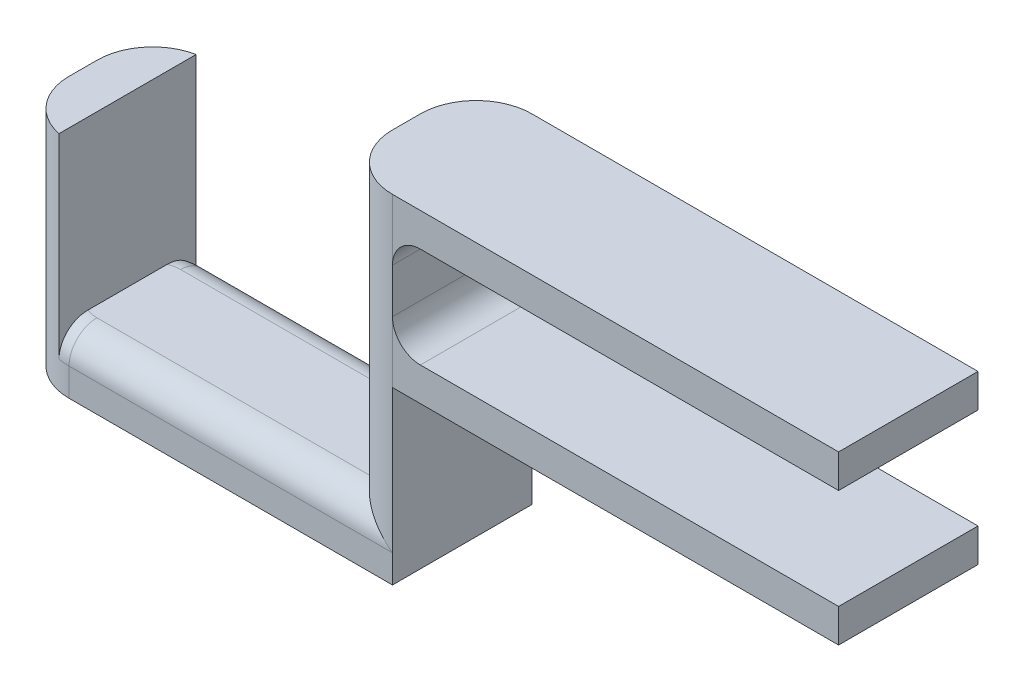
SolidWorks part; units mm, degrees
ref_plane "前基準面" through (0, 0, 0) normal (0, 0, 1) x (1, 0, 0)
ref_plane "上基準面" through (0, 0, 0) normal (0, 1, 0) x (1, 0, 0)
ref_plane "右基準面" through (0, 0, 0) normal (1, 0, 0) x (0, 0, -1)
sketch "草圖1" plane through (0, 0, 0) normal (0, 0, 1) x (1, 0, 0)
  line L2 (-55.2938, 11.9758) -> (-55.2938, -28.0242)
  line L4 (-47.2938, 11.9758) -> (-47.2938, -18.0242)
  line L5 (-47.2938, -18.0242) -> (2.7062, -18.0242)
  line L7 (-55.2938, -28.0242) -> (12.7062, -28.0242)
  line L10 (2.7062, -18.0242) -> (2.7062, 32.6478)
  line L12 (12.7062, -28.0242) -> (12.7062, 2.6478)
  line L13 (2.7062, 32.6478) -> (92.7062, 32.6478)
  line L15 (17.7062, 26.6478) -> (92.7062, 26.6478)
  line L16 (92.7062, 32.6478) -> (92.7062, 26.6478)
  line L17 (17.7062, 8.6478) -> (92.7062, 8.6478)
  line L19 (12.7062, 2.6478) -> (92.7062, 2.6478)
  line L20 (92.7062, 8.6478) -> (92.7062, 2.6478)
  line L21 (-55.2938, 11.9758) -> (-47.2938, 11.9758)
  line L24 (12.7062, 21.6478) -> (12.7062, 13.6478)
  arc A0 (17.7062, 26.6478) -> (12.7062, 21.6478) centre (17.7062, 21.6478) ccw
  arc A1 (17.7062, 8.6478) -> (12.7062, 13.6478) centre (17.7062, 13.6478) cw
  point P1 (92.7062, 29.6478)
  dimension "D12" = 80
  dimension "D1" = 50
  dimension "D2" = 10
  dimension "D3" = 10
  dimension "D4" = 8
  dimension "D5" = 6
  dimension "D6" = 6
  dimension "D7" = 30
  dimension "D8" = 40
  dimension "D9" = 10
  dimension "D10" = 80
  dimension "D11" = 18
extrude "填料-伸長1" add sketch "草圖1" along normal blind 25
fillet "圓角2" radius 10 1 edges at (-55.2938, -8.0242, 0)
fillet "圓角3" radius 10 1 edges at (-55.2938, -8.0242, 25)
fillet "圓角4" radius 10 2 edges at (2.7062, 7.3118, 25) (2.7062, 7.3118, 0)
fillet "圓角6" radius 5 4 edges at (-46.2989, -18.0242, 24.9494) (-46.2989, -18.0242, 0.0506) (-16.2938, -18.0242, 25) (-16.2938, -18.0242, 0)
